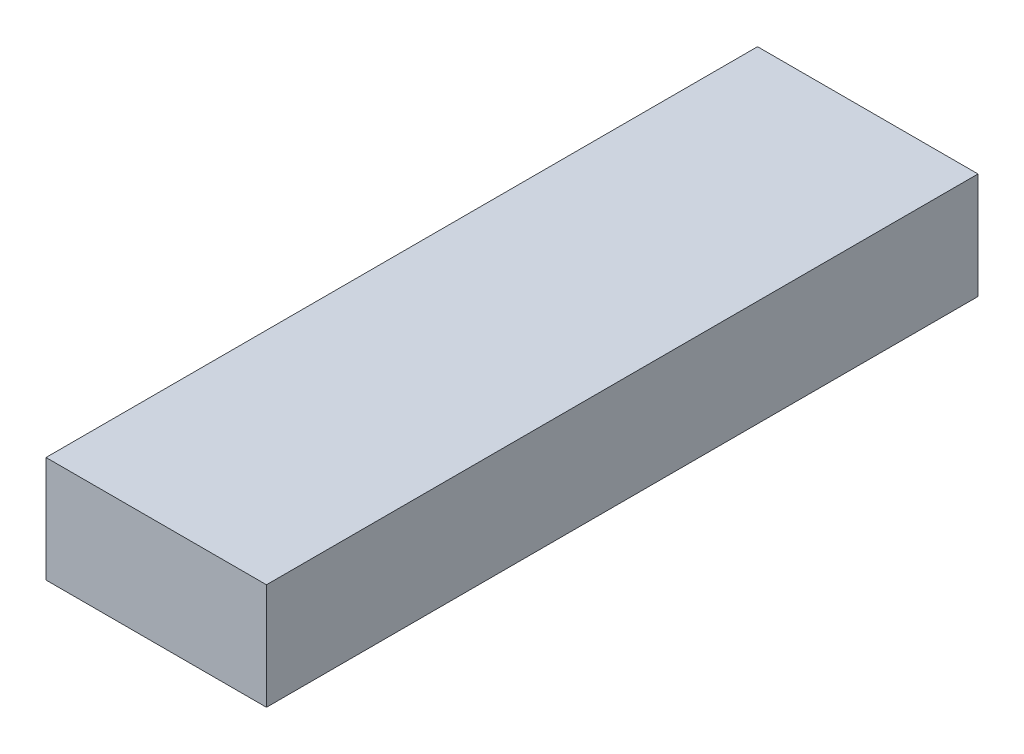
SolidWorks part; units mm, degrees
ref_plane "Front Plane" through (0, 0, 0) normal (0, 0, 1) x (1, 0, 0)
ref_plane "Top Plane" through (0, 0, 0) normal (0, 1, 0) x (1, 0, 0)
ref_plane "Right Plane" through (0, 0, 0) normal (1, 0, 0) x (0, 0, -1)
sketch "Sketch1" plane through (0, 0, 0) normal (0, 0, 1) x (1, 0, 0)
  line L1 (-24.003, -11.557) -> (24.003, -11.557)
  line L2 (-24.003, -11.557) -> (-24.003, 11.557)
  line L3 (-24.003, 11.557) -> (24.003, 11.557)
  line L4 (24.003, -11.557) -> (24.003, 11.557)
  line L5 (-24.003, -11.557) -> (24.003, 11.557) construction
  line L6 (-24.003, 11.557) -> (24.003, -11.557) construction
  point P0 (0, 0)
  dimension "D1" = 48.006
  dimension "D2" = 23.114
extrude "Boss-Extrude1" add sketch "Sketch1" along normal blind 77.47 and the other way blind 77.47
